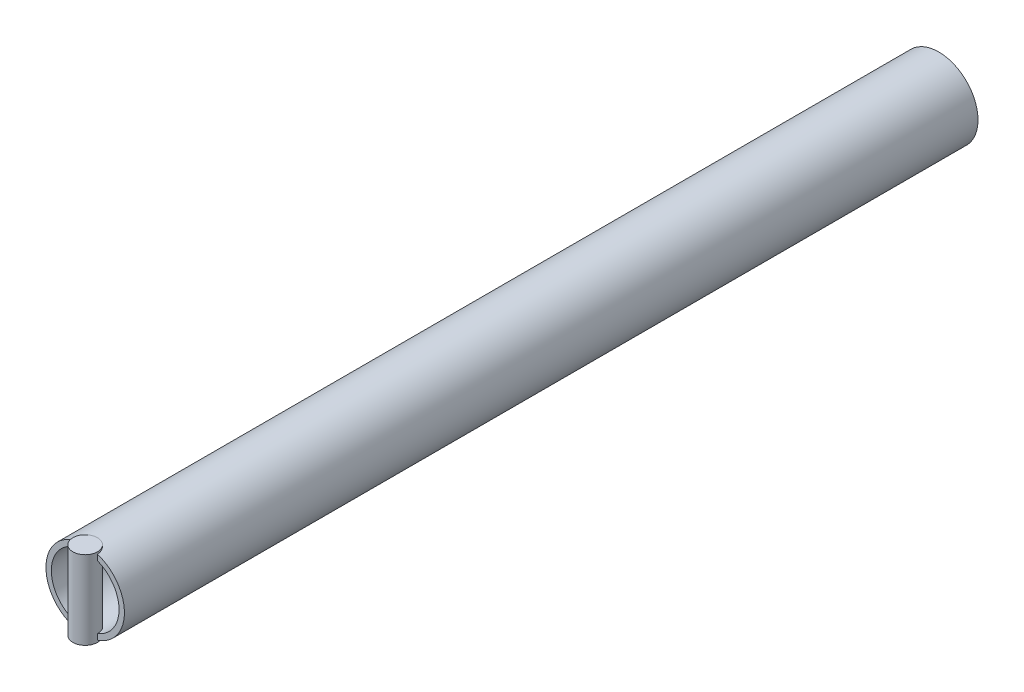
SolidWorks part; units mm, degrees
ref_plane "Front Plane" through (0, 0, 0) normal (0, 0, 1) x (1, 0, 0)
ref_plane "Top Plane" through (0, 0, 0) normal (0, 1, 0) x (1, 0, 0)
ref_plane "Right Plane" through (0, 0, 0) normal (1, 0, 0) x (0, 0, -1)
sketch "Sketch1" plane through (0, 0, 0) normal (0, 0, 1) x (1, 0, 0)
  circle A0 centre (0, 0) radius 8
  circle A1 centre (0, 0) radius 6.9
  dimension "D1" = 16
  dimension "D2" = 13.8
extrude "Boss-Extrude1" add sketch "Sketch1" along normal blind 174
sketch "Sketch2" plane through (0, 0, 0) normal (0, 1, 0) x (1, 0, 0)
  line L0 (-8, -174) -> (8, -174) construction
  circle A1 centre (0, -174) radius 2.5
extrude "Boss-Extrude2" add sketch "Sketch2" along normal blind 8 and the other way blind 8
